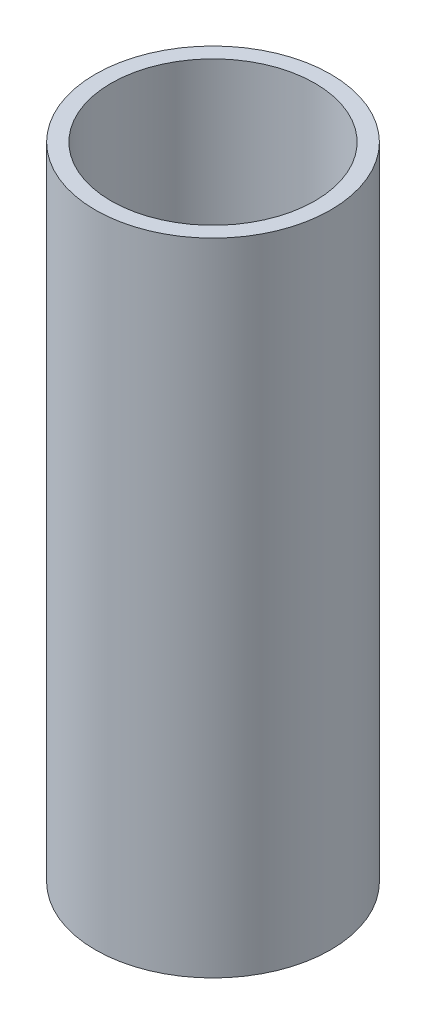
SolidWorks part; units mm, degrees
ref_plane "Front Plane" through (0, 0, 0) normal (0, 0, 1) x (1, 0, 0)
ref_plane "Top Plane" through (0, 0, 0) normal (0, 1, 0) x (1, 0, 0)
ref_plane "Right Plane" through (0, 0, 0) normal (1, 0, 0) x (0, 0, -1)
sketch "Sketch1" plane through (0, 0, 0) normal (0, 1, 0) x (1, 0, 0)
  circle A0 centre (0, 0) radius 40
  dimension "SLEEVE_OD" = 80
extrude "Boss-Extrude1" add sketch "Sketch1" along normal blind 217.8093
sketch "Sketch2" plane through (0, 0, 0) normal (0, 1, 0) x (1, 0, 0)
  circle A0 centre (0, 0) radius 34.6522
  dimension "BORE_D" = 69.3043
extrude "Cut-Extrude1" cut sketch "Sketch2" along normal through all
chamfer "Chamfer1" distance 3.7377 angle 30 rebuild error yes
